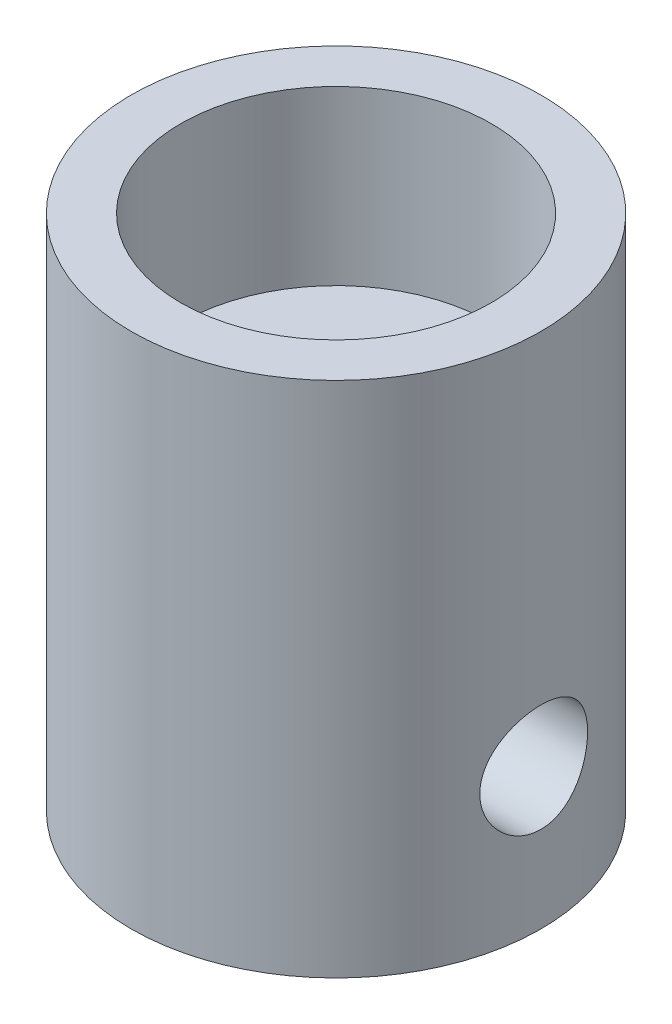
SolidWorks part; units mm, degrees
ref_plane "Plano frontal" through (0, 0, 0) normal (0, 0, 1) x (1, 0, 0)
ref_plane "Plano superior" through (0, 0, 0) normal (0, 1, 0) x (1, 0, 0)
ref_plane "Plano direito" through (0, 0, 0) normal (1, 0, 0) x (0, 0, -1)
sketch "Esboço1" plane through (0, 0, 0) normal (0, 1, 0) x (1, 0, 0)
  circle A0 centre (0, 0) radius 4.75
  dimension "D1" = 9.5
extrude "Ressalto-extrusão1" add sketch "Esboço1" along normal blind 12
sketch "Esboço6" plane through (0, 12, 0) normal (0, 1, 0) x (1, 0, 0)
  circle A0 centre (0, 0) radius 3.6
  dimension "D1" = 7.2
extrude "Corte-extrusão5" cut sketch "Esboço6" against normal blind 4
sketch "Esboço8" plane through (0, 0, 0) normal (0, -1, 0) x (1, 0, 0)
  line L0 (-2, 1.8875) -> (-2, -1.8875)
  line L1 (2, 1.8875) -> (2, -1.8875)
  arc A0 (-2, -1.8875) -> (2, -1.8875) centre (0, 0) ccw
  arc A1 (2, 1.8875) -> (-2, 1.8875) centre (0, 0) ccw
  dimension "D1" = 5.5
  dimension "D2" = 2
  dimension "D3" = 2
extrude "Corte-extrusão6" cut sketch "Esboço8" against normal offset from surface (7 mm away) 1 up to face at (0, 8, 3.6)
sketch "Esboço9" plane through (0, 0, 0) normal (1, 0, 0) x (0, 0, -1)
  circle A0 centre (0, 3.25) radius 1.25
  dimension "D1" = 3.25
  dimension "D2" = 2.5
extrude "Corte-extrusão7" cut sketch "Esboço9" against normal through all both and the other way through all
sketch "Esboço10" plane through (0, 0, 0) normal (0, -1, 0) x (1, 0, 0)
  circle A0 centre (0, 0) radius 2.75
extrude "Corte-extrusão8" cut sketch "Esboço10" against normal blind 1.25
